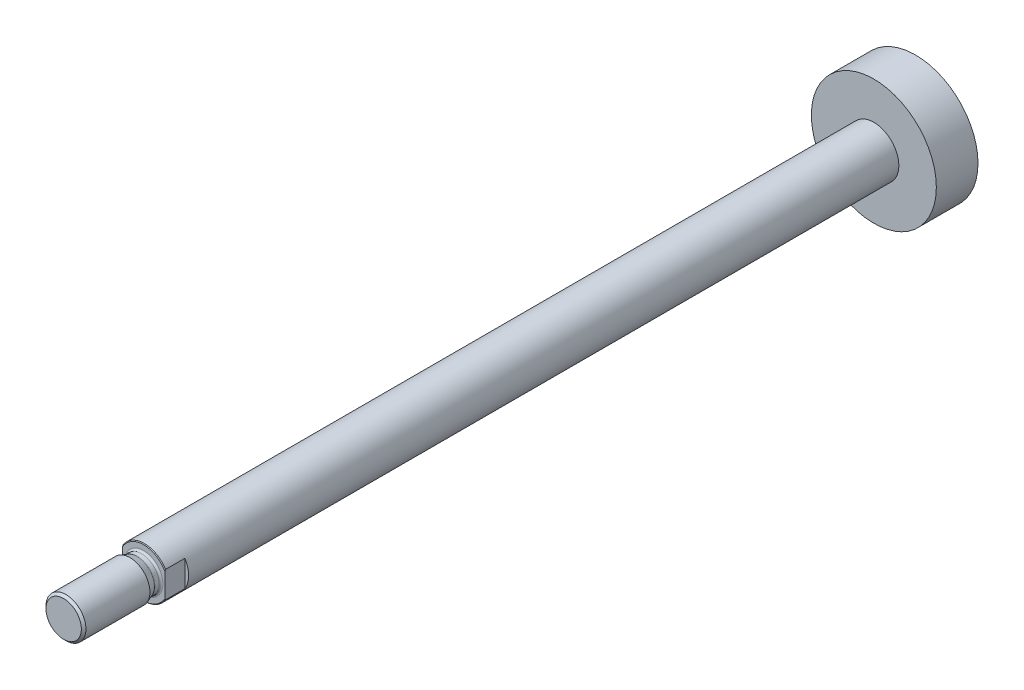
SolidWorks part; units mm, degrees
ref_plane "Front Plane" through (0, 0, 0) normal (0, 0, 1) x (1, 0, 0)
ref_plane "Top Plane" through (0, 0, 0) normal (0, 1, 0) x (1, 0, 0)
ref_plane "Right Plane" through (0, 0, 0) normal (1, 0, 0) x (0, 0, -1)
sketch "Sketch1" plane through (0, 0, 0) normal (1, 0, 0) x (0, 0, -1)
  line L0 (-35.8, 0) -> (-35.8, 9.7172)
  line L1 (-35.8, 9.7172) -> (-35.5172, 10)
  line L2 (-35.5172, 10) -> (256.3333, 10)
  line L3 (256.3333, 10) -> (256.3333, 25)
  line L4 (256.3333, 25) -> (273, 25)
  line L5 (273, 25) -> (273, 0)
  line L6 (273, 0) -> (-35.8, 0)
  line L7 (273, 0) -> (-35.8, 0) construction
revolve "Revolve1" add sketch "Sketch1" angle 360 about L7 reverse direction yes
ref_plane "Plane1" through (0, 0, -256.3333) normal (0, 0, 1) x (1, 0, 0)
sketch "Sketch2" plane through (0, 0, 0) normal (0, 1, 0) x (1, 0, 0)
  line L0 (-17, -61.8) -> (17, -61.8)
  line L1 (17, -61.8) -> (17, -27.8)
  line L2 (17, -27.8) -> (8.5, -27.8)
  line L3 (8.5, -27.8) -> (8.5, -43.8)
  line L4 (8.5, -43.8) -> (-8.5, -43.8)
  line L5 (-8.5, -43.8) -> (-8.5, -27.8)
  line L6 (-8.5, -27.8) -> (-17, -27.8)
  line L7 (-17, -27.8) -> (-17, -61.8)
extrude "Cut-Extrude1" cut sketch "Sketch2" along normal blind 17 and the other way blind 17
sketch "Sketch3" plane through (0, 0, 0) normal (1, 0, 0) x (0, 0, -1)
  line L0 (-67.8, 0) -> (-67.8, 7.08)
  line L1 (-67.8, 7.08) -> (-66.88, 8)
  line L2 (-66.88, 8) -> (-41.2849, 8)
  line L3 (-41.2849, 8) -> (-38.5243, 6.9952)
  line L4 (-38.2678, 6.95) -> (-36.55, 6.95)
  line L5 (-35.8, 7.7) -> (-35.05, 7.7)
  line L6 (-35.05, 7.7) -> (-35.05, 0)
  line L7 (-35.05, 0) -> (-67.8, 0)
  line L8 (-35.05, 0) -> (-67.8, 0) construction
  arc A0 (-38.5243, 6.9952) -> (-38.2678, 6.95) centre (-38.2678, 7.7) ccw
  arc A1 (-36.55, 6.95) -> (-35.8, 7.7) centre (-36.55, 7.7) ccw
revolve "Revolve2" add sketch "Sketch3" angle 360 about L8 reverse direction yes
cosmetic thread "Cosmetic Thread1" parameters "D1"=29.0428, "D2"=14.16
ref_plane "Plane2" through (0, 0, -273) normal (0, 0, 1) x (1, 0, 0)
ref_plane "Plane3" through (0, 0, 49.8) normal (0, 0, 1) x (1, 0, 0)
ref_plane "Plane4" through (0, 0, 49.8) normal (0, 0, 1) x (1, 0, 0)
ref_plane "FDT_PIRODACC XY" through (0, 0, 49.8) normal (0, 0, 1) x (1, 0, 0)
ref_plane "FDT_PIRODACC XZ" through (0, 0, 0) normal (0, -1, 0) x (-1, 0, 0)
ref_plane "FDT_PIRODACC YZ" through (0, 0, 0) normal (1, 0, 0) x (0, 0, -1)
ref_axis "FDT_PIRODACC X" through (-80.9, 0, 49.8) along (1, 0, 0)
ref_axis "FDT_PIRODACC Y" through (0, -50, 49.8) along (0, 1, 0)
ref_axis "FDT_PIRODACC Z" through (0, 0, 80.9) along (0, 0, -1)
sketch3d "FDT_PIRODACC"
  point P0 (0, 0, 49.8)
ref_plane "NUT XY" through (0, 0, 49.8) normal (0, 0, -1) x (-1, 0, 0)
ref_plane "NUT XZ" through (0, 0, 0) normal (0, 1, 0) x (1, 0, 0)
ref_plane "NUT YZ" through (0, 0, 0) normal (1, 0, 0) x (0, 0, -1)
ref_axis "NUT X" through (-80.9, 0, 49.8) along (1, 0, 0)
ref_axis "NUT Y" through (0, 50, 49.8) along (0, -1, 0)
ref_axis "NUT Z" through (0, 0, -80.9) along (0, 0, 1)
sketch3d "NUT"
  point P0 (0, 0, 49.8)
ref_plane "P XY" through (0, 0, -273) normal (0, 0, -1) x (-1, 0, 0)
ref_plane "P XZ" through (0, 0, 0) normal (-1, 0, 0) x (0, 0, 1)
ref_plane "P YZ" through (0, 0, 0) normal (0, 1, 0) x (1, 0, 0)
ref_axis "P X" through (0, -50, -273) along (0, 1, 0)
ref_axis "P Y" through (-80.9, 0, -273) along (1, 0, 0)
ref_axis "P Z" through (0, 0, -50) along (0, 0, 1)
sketch3d "P"
  point P0 (0, 0, -273)
other "Freeze***"
